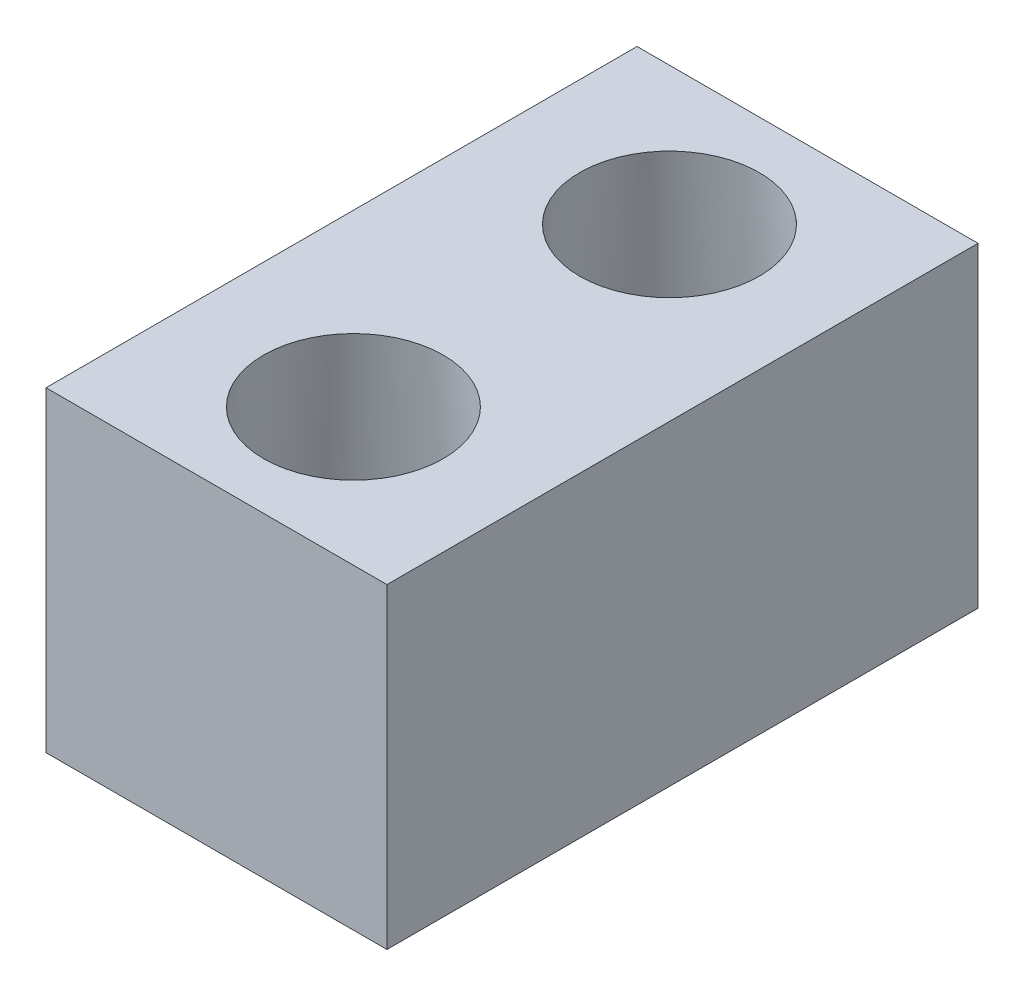
SolidWorks part; units mm, degrees
ref_plane "Front Plane" through (0, 0, 0) normal (0, 0, 1) x (1, 0, 0)
ref_plane "Top Plane" through (0, 0, 0) normal (0, 1, 0) x (1, 0, 0)
ref_plane "Right Plane" through (0, 0, 0) normal (1, 0, 0) x (0, 0, -1)
sketch "Sketch2" plane through (0, 0, 0) normal (0, 1, 0) x (1, 0, 0)
  line L1 (27.4, -48.2955) -> (-27.4, -48.2955)
  line L2 (27.4, -48.2955) -> (27.4, 46.7045)
  line L3 (27.4, 46.7045) -> (-27.4, 46.7045)
  line L4 (-27.4, -48.2955) -> (-27.4, 46.7045)
  point P0 (0, 0)
  dimension "D1" = 54.8
  dimension "D3" = 95
extrude "Boss-Extrude1" add sketch "Sketch2" along normal blind 50.8 contours L4 L3 L2 L1
sketch "Sketch3" plane through (0, 0, 0) normal (0, -1, 0) x (1, 0, 0)
  line L0 (27.4, 48.2955) -> (-27.4, 48.2955) construction
  line L2 (27.4, 48.2955) -> (27.4, -46.7045) construction
  line L3 (27.4, -46.7045) -> (-27.4, -46.7045) construction
  circle A0 centre (-0.0295, 26.2549) radius 19.05
  circle A1 centre (-0.0295, -24.5451) radius 19.05
  dimension "D1" = 38.1
  dimension "D2" = 22.0406
  dimension "D3" = 27.4295
  dimension "D4" = 22.1594
  dimension "D5" = 27.4295
sketch "Sketch4" plane through (0, 50.8, 0) normal (0, 1, 0) x (1, 0, 0)
  circle A0 centre (-0.0295, 24.5451) radius 14.4358
  circle A1 centre (-0.0295, -26.2549) radius 14.4358
  point P0 (-0.0295, 24.5451)
  point P2 (-0.0295, -26.2549)
  dimension "D1" = 28.8716
sketch "Sketch5" plane through (0, 50.8, 0) normal (0, 1, 0) x (1, 0, 0)
  text T0 "top"
sketch "Sketch6" plane through (0, 0, 0) normal (0, -1, 0) x (1, 0, 0)
  text T0 "bottom"
extrude "Cut-Extrude1" cut sketch "Sketch3" against normal blind 5
loft "Cut-Loft1" cut section "Sketch4" section edge at (-0.0295, 5, -5.4951) connector at (-10.4032, 50.8, -34.584) connector at (-13.9707, 5, -37.5276)
loft "Cut-Loft2" cut section "Sketch4<166>" section edge at (-0.0295, 5, 7.2049) connector at (-14.4042, 50.8, 24.9284) connector at (-19.0005, 5, 24.5223)
sketch "Sketch4<166>" plane through (0, 50.8, 0) normal (0, 1, 0) x (1, 0, 0) same geometry as "Sketch4"
